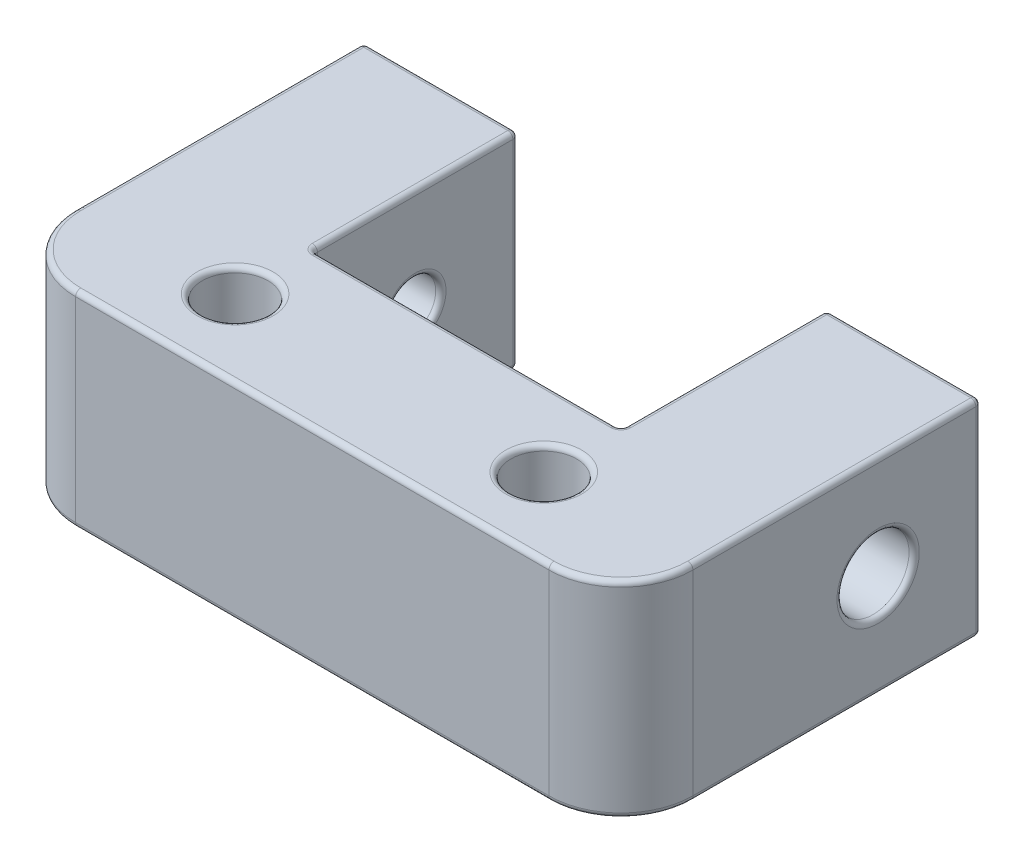
SolidWorks part; units mm, degrees
ref_plane "Front Plane" through (0, 0, 0) normal (0, 0, 1) x (1, 0, 0)
ref_plane "Top Plane" through (0, 0, 0) normal (0, 1, 0) x (1, 0, 0)
ref_plane "Right Plane" through (0, 0, 0) normal (1, 0, 0) x (0, 0, -1)
sketch "Sketch1" plane through (0, 0, 0) normal (0, 1, 0) x (1, 0, 0)
  line L1 (-30, -12.5) -> (30, -12.5)
  line L2 (-30, -12.5) -> (-30, 12.5)
  line L3 (-30, 12.5) -> (30, 12.5)
  line L4 (30, -12.5) -> (30, 12.5)
  line L5 (-30, -12.5) -> (30, 12.5) construction
  line L6 (-30, 12.5) -> (30, -12.5) construction
  line L9 (-15, -7.5) -> (15, -7.5)
  line L10 (-25, 7.5) -> (25, 7.5) construction
  line L11 (-25, -7.5) -> (-25, 7.5) construction
  line L12 (25, -7.5) -> (25, 7.5) construction
  line L13 (-30, -14) -> (30, -14) construction
  line L14 (-30, -12.5) -> (30, -12.5)
  line L15 (-30, -12.5) -> (-30, -15.5)
  line L16 (-23, -22.5) -> (23, -22.5)
  line L17 (30, -12.5) -> (30, -15.5)
  line L18 (-30, -22.5) -> (0, -22.5) construction
  line L19 (0, -22.5) -> (0, 12.5) construction
  line L20 (-15, 0) -> (15, 0) construction
  line L21 (-15, 12.5) -> (-15, -7.5)
  line L22 (15, 12.5) -> (15, -7.5)
  line L23 (-25, -7.5) -> (25, -7.5) construction
  line L24 (-15, -15) -> (15, -15) construction
  circle A0 centre (-15, -15) radius 3.2
  circle A1 centre (15, -15) radius 3.2
  arc A2 (23, -22.5) -> (30, -15.5) centre (23, -15.5) ccw
  arc A3 (-30, -15.5) -> (-23, -22.5) centre (-23, -15.5) ccw
  point P0 (0, 0)
  point P19 (-15, -15)
  point P31 (0, 0)
  dimension "D5" = 6.4
  dimension "D6" = 7
  dimension "D1" = 25
  dimension "D2" = 60
  dimension "D4" = 10
extrude "Boss-Extrude1" add sketch "Sketch1" along normal blind 20 contours L9 L3 L2 L1 L4 | L15 A3 L16 A2 L17 L1 A1 A0 region at (-29.35, 0, 0) region at (0, 0, 17.6319)
sketch "Sketch2" plane through (-30, 0, 0) normal (-1, 0, 0) x (0, 0, 1)
  line L0 (-12.5, 10) -> (-2.5, 10) construction
  line L1 (-12.5, 20) -> (-12.5, 0) construction
  circle A0 centre (-2.5, 10) radius 2.5
  dimension "D2" = 5
  dimension "D1" = 10
extrude "Cut-Extrude1" cut sketch "Sketch2" against normal blind 70
fillet "Fillet1" radius 0.5 34 edges at (-15, 0, 18.2) (15, 0, 18.2) (-27.9497, 0, 20.4497) (0, 0, 22.5) (27.9497, 0, 20.4497) (0, 0, 7.5) (30, 0, 1.5) (30, 10, 0) (-22.5, 0, -12.5) (-30, 10, -12.5) (-30, 0, 1.5) (-30, 10, 0) (30, 10, -12.5) (22.5, 0, -12.5) (-15, 20, 18.2) (15, 20, 18.2) (22.5, 20, -12.5) (30, 20, 1.5) (27.9497, 20, 20.4497) (0, 20, 22.5) (-27.9497, 20, 20.4497) (-30, 20, 1.5) (-22.5, 20, -12.5) (0, 20, 7.5) (15, 10, 7.5) (-15, 10, 7.5) (15, 0, -2.5) (-15, 0, -2.5) (-15, 10, -12.5) (15, 10, -12.5) (-15, 20, -2.5) (15, 20, -2.5) (-15, 10, -5) (15, 10, -5)
sketch "Sketch3" plane through (-30, 0, 0) normal (-1, 0, 0) x (0, 0, 1)
  line L1 (2.6962, 10) -> (0.0981, 14.5)
  line L2 (0.0981, 14.5) -> (-5.0981, 14.5)
  line L3 (-5.0981, 14.5) -> (-7.6962, 10)
  line L4 (-7.6962, 10) -> (-5.0981, 5.5)
  line L5 (-5.0981, 5.5) -> (0.0981, 5.5)
  line L6 (0.0981, 5.5) -> (2.6962, 10)
  circle A0 centre (-2.5, 10) radius 4.5 construction
  dimension "D1" = 9
sketch "Sketch4" plane through (30, 0, 0) normal (1, 0, 0) x (0, 0, -1)
  circle A0 centre (2.5, 10) radius 3.5
  dimension "D1" = 7
extrude "Cut-Extrude2" cut sketch "Sketch4" against normal blind 10
extrude "Cut-Extrude3" cut sketch "Sketch3" against normal blind 10
fillet "Fillet2" radius 0.5 9 edges at (-30, 12.25, 1.3971) (-30, 14.5, -2.5) (-30, 12.25, -6.3971) (-30, 7.75, -6.3971) (-30, 5.5, -2.5) (-30, 7.75, 1.3971) (30, 10, -6) (20, 10, -5) (20, 10, -6)
